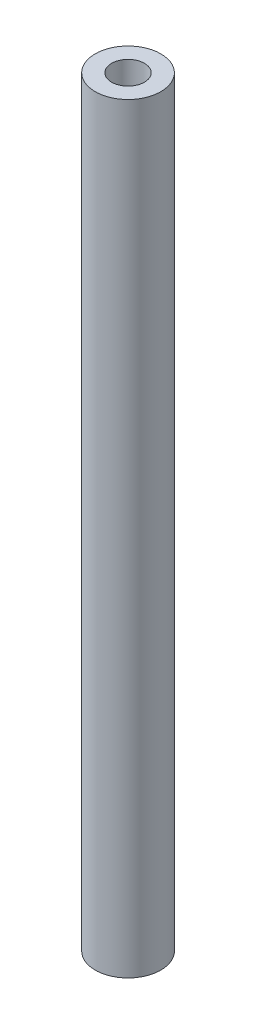
SolidWorks part; units mm, degrees
ref_plane "Front Plane" through (0, 0, 0) normal (0, 0, 1) x (1, 0, 0)
ref_plane "Top Plane" through (0, 0, 0) normal (0, 1, 0) x (1, 0, 0)
ref_plane "Right Plane" through (0, 0, 0) normal (1, 0, 0) x (0, 0, -1)
sketch "Sketch1" plane through (0, 0, 0) normal (0, 1, 0) x (1, 0, 0)
  circle A0 centre (0, 0) radius 5
  dimension "D1" = 10
extrude "Boss-Extrude1" add sketch "Sketch1" along normal blind 116
sketch "Sketch2" plane through (0, 116, 0) normal (0, 1, 0) x (1, 0, 0)
  circle A0 centre (0, 0) radius 2.5
  dimension "D1" = 5
extrude "Cut-Extrude1" cut sketch "Sketch2" against normal blind 10
sketch "Sketch3" plane through (0, 0, 0) normal (0, -1, 0) x (1, 0, 0)
  circle A0 centre (0, 0) radius 2.5
  dimension "D1" = 5
extrude "Cut-Extrude2" cut sketch "Sketch3" against normal blind 10
